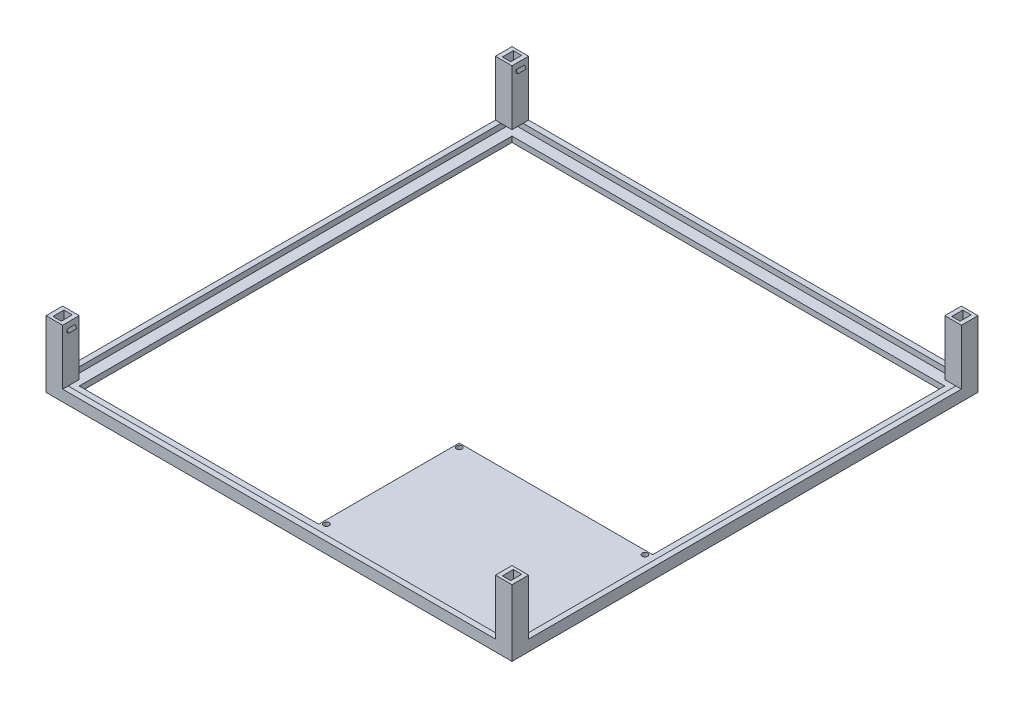
SolidWorks part; units mm, degrees
ref_plane "Front Plane" through (0, 0, 0) normal (0, 0, 1) x (1, 0, 0)
ref_plane "Top Plane" through (0, 0, 0) normal (0, 1, 0) x (1, 0, 0)
ref_plane "Right Plane" through (0, 0, 0) normal (1, 0, 0) x (0, 0, -1)
sketch "Sketch1" plane through (0, 0, 0) normal (0, 1, 0) x (1, 0, 0)
  line L0 (-84.1688, -84.1688) -> (-84.1688, 84.1688)
  line L1 (-80.1687, -80.1688) -> (80.1688, -80.1688) construction
  line L2 (-80.1687, -80.1688) -> (-80.1687, 80.1688) construction
  line L3 (-80.1687, 80.1688) -> (80.1688, 80.1688) construction
  line L4 (80.1688, -80.1688) -> (80.1688, 80.1688) construction
  line L5 (-80.1687, -80.1688) -> (80.1688, 80.1688) construction
  line L6 (-80.1687, 80.1688) -> (80.1688, -80.1688) construction
  line L7 (-84.1688, 84.1688) -> (84.1688, 84.1688)
  line L8 (84.1687, -84.1688) -> (84.1688, 84.1688)
  line L9 (-84.1688, -84.1688) -> (84.1687, -84.1688)
  line L10 (-78.1687, 78.1687) -> (78.1688, 78.1687)
  line L11 (78.1688, -78.1687) -> (78.1688, 78.1687)
  line L12 (-78.1687, -78.1687) -> (78.1688, -78.1687)
  line L13 (-78.1687, -78.1687) -> (-78.1687, 78.1687)
  line L14 (-82.1687, -82.1688) -> (-82.1687, 82.1688)
  line L15 (-82.1687, 82.1688) -> (82.1688, 82.1688)
  line L16 (82.1688, -82.1688) -> (82.1688, 82.1688)
  line L17 (-82.1687, -82.1688) -> (82.1688, -82.1688)
  line L18 (8.3187, -27.3688) -> (78.1688, -78.1687) construction
  line L19 (78.1688, -78.1687) -> (8.3187, -78.1688)
  line L20 (78.1688, -78.1687) -> (78.1687, -27.3687)
  line L21 (78.1687, -27.3687) -> (8.3187, -27.3688)
  line L22 (8.3187, -78.1688) -> (8.3187, -27.3688)
  line L23 (78.1687, -27.3687) -> (8.3187, -78.1688) construction
  line L24 (9.7188, -28.7688) -> (9.7188, -27.3688) construction
  line L25 (9.7188, -27.3688) -> (9.7188, -28.7688)
  line L26 (8.3187, -28.7688) -> (9.7188, -28.7688) construction
  line L27 (43.2437, -27.3688) -> (43.2437, -78.1687) construction
  line L28 (8.3187, -52.7688) -> (78.1688, -52.7688) construction
  circle A0 centre (9.7188, -28.7688) radius 1
  circle A1 centre (9.7188, -76.7687) radius 1
  circle A2 centre (76.7688, -76.7687) radius 1
  circle A3 centre (76.7687, -28.7688) radius 1
  point P0 (0, 0)
  dimension "D7" = 2
  dimension "D1" = 160.3375
  dimension "D5" = 69.85
  dimension "D6" = 50.8
  dimension "D8" = 1.4
  dimension "D2" = 4
  dimension "D3" = 2
  dimension "D4" = 2
extrude "Boss-Extrude1" add sketch "Sketch1" along normal blind 2 contours L14 L17 L16 L15 L12 L13 L10 L11 | A0 L21 L22 L12 L11 A1 A2 A3 region at (43.2438, 0, 52.7687) region at (-79.8447, 0, 0)
extrude "Boss-Extrude2" add sketch "Sketch1<3>" along normal blind 4 contours L0 L9 L8 L7 L17 L14 L15 L16 region at (-83.9307, 0, 0)
sketch "Sketch1<3>" plane through (0, 0, 0) normal (0, 1, 0) x (1, 0, 0) same geometry as "Sketch1"
sketch "Sketch2" plane through (0, 4, 0) normal (0, 1, 0) x (1, 0, 0)
  line L1 (-84.1688, 84.1688) -> (-78.1687, 84.1688)
  line L2 (-84.1688, 84.1688) -> (-84.1688, 78.1687)
  line L3 (-84.1688, 78.1687) -> (-78.1687, 78.1687)
  line L4 (-78.1687, 84.1688) -> (-78.1687, 78.1687)
  line L5 (0, -2.2) -> (0, 2.2) construction
  line L6 (84.1688, 78.1687) -> (78.1687, 78.1687)
  line L7 (84.1688, 84.1688) -> (84.1688, 78.1687)
  line L8 (84.1688, 84.1688) -> (78.1687, 84.1688)
  line L9 (78.1687, 84.1688) -> (78.1687, 78.1687)
  line L10 (-2.2, 0) -> (2.2, 0) construction
  line L11 (78.1687, -84.1688) -> (78.1687, -78.1687)
  line L12 (84.1688, -84.1688) -> (78.1687, -84.1688)
  line L13 (84.1688, -84.1688) -> (84.1688, -78.1687)
  line L14 (84.1688, -78.1687) -> (78.1687, -78.1687)
  line L15 (-78.1687, -84.1688) -> (-78.1687, -78.1687)
  line L16 (-84.1688, -78.1687) -> (-78.1687, -78.1687)
  line L17 (-84.1688, -84.1688) -> (-84.1688, -78.1687)
  line L18 (-84.1688, -84.1688) -> (-78.1687, -84.1688)
extrude "Boss-Extrude3" add sketch "Sketch2" along normal blind 20
sketch "Sketch3" plane through (0, 24, 0) normal (0, 1, 0) x (1, 0, 0)
  line L0 (84.1688, -84.1688) -> (84.1688, -78.1687) construction
  line L1 (82.6688, -83.1688) -> (79.6687, -83.1688)
  line L2 (82.6688, -83.1688) -> (82.6688, -79.1688)
  line L3 (82.6688, -79.1688) -> (79.6687, -79.1688)
  line L4 (79.6687, -83.1688) -> (79.6687, -79.1688)
  line L5 (78.1687, -78.1687) -> (78.1687, -84.1688) construction
  line L6 (78.1687, -84.1688) -> (84.1688, -84.1688) construction
  line L7 (84.1688, -78.1687) -> (78.1687, -78.1687) construction
  line L8 (-13.2, 0) -> (13.2, 0) construction
  line L9 (79.6687, 83.1688) -> (79.6687, 79.1688)
  line L10 (82.6688, 79.1688) -> (79.6687, 79.1688)
  line L11 (82.6688, 83.1688) -> (82.6688, 79.1688)
  line L12 (82.6688, 83.1688) -> (79.6687, 83.1688)
  line L13 (0, -13.2) -> (0, 13.2) construction
  line L14 (-82.6688, 83.1688) -> (-79.6687, 83.1688)
  line L15 (-82.6688, 83.1688) -> (-82.6688, 79.1688)
  line L16 (-82.6688, 79.1688) -> (-79.6687, 79.1688)
  line L17 (-79.6687, 83.1688) -> (-79.6687, 79.1688)
  line L18 (-79.6687, -83.1688) -> (-79.6687, -79.1688)
  line L19 (-82.6688, -79.1688) -> (-79.6687, -79.1688)
  line L20 (-82.6688, -83.1688) -> (-82.6688, -79.1688)
  line L21 (-82.6688, -83.1688) -> (-79.6687, -83.1688)
  dimension "D1" = 1.5
  dimension "D2" = 1.5
  dimension "D3" = 1
  dimension "D4" = 1
extrude "Cut-Extrude1" cut sketch "Sketch3" against normal blind 4
sketch "Sketch4" plane through (0, 0, 78.1687) normal (0, 0, -1) x (-1, 0, 0)
  line L0 (-78.1687, 24) -> (-78.1687, 22)
  line L1 (-78.1687, 24) -> (-78.1687, 4) construction
  line L2 (-78.1687, 22) -> (-78.1687, 21)
  line L3 (-78.1687, 21) -> (-77.5687, 21)
  line L4 (-77.5687, 21) -> (-78.1687, 22)
  line M6 (-78.1687, 4) -> (-78.1687, 24)
  dimension "D1" = 2
  dimension "D2" = 1
  dimension "D3" = 0.6
extrude "Boss-Extrude4" add sketch "Sketch4" against normal blind 3 from offset 1.5 contours L3 L4 M6 region at (77.9687, 21.3333, 78.1687) offset against normal yes
mirror "Mirror1" about plane through (0, 0, 0) normal (1, 0, 0) of "Boss-Extrude4"
mirror "Mirror2" about plane through (0, 0, 0) normal (0, 0, 1) of "Mirror1"
